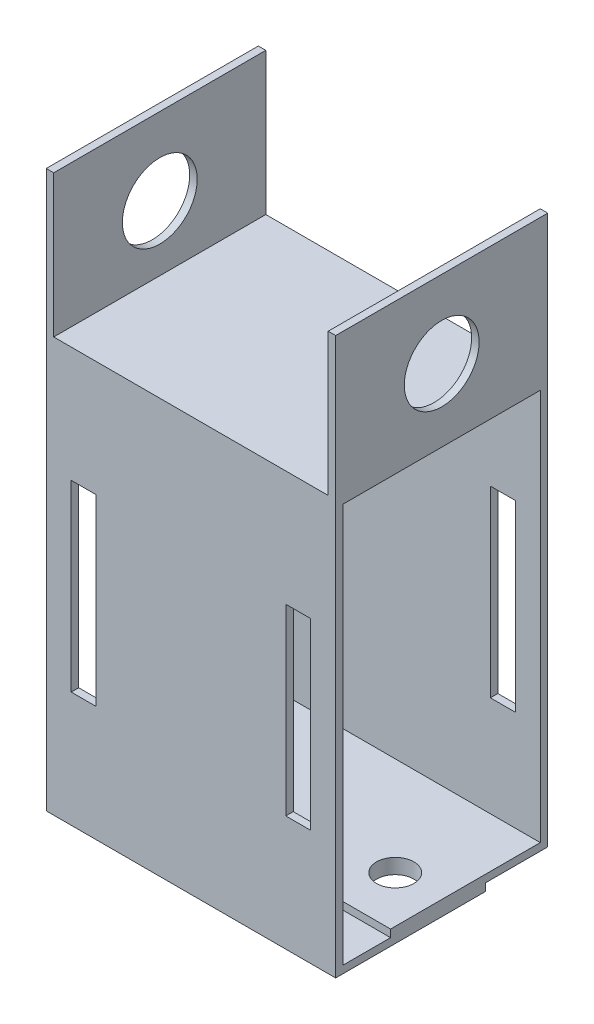
SolidWorks part; units mm, degrees
material "6061 Alloy"
ref_plane "Front Plane" through (0, 0, 0) normal (0, 0, 1) x (1, 0, 0)
ref_plane "Top Plane" through (0, 0, 0) normal (0, 1, 0) x (1, 0, 0)
ref_plane "Right Plane" through (0, 0, 0) normal (1, 0, 0) x (0, 0, -1)
sketch "Sketch1" plane through (0, 0, 0) normal (0, 1, 0) x (1, 0, 0)
  line L0 (0, -1000) -> (0, 49000) construction
  line L1 (13.97, -10.795) -> (-13.97, -10.795)
  line L2 (13.97, -10.795) -> (13.97, 10.795)
  line L3 (13.97, 10.795) -> (-13.97, 10.795)
  line L4 (-13.97, -10.795) -> (-13.97, 10.795)
  line L5 (13.97, -10.795) -> (-13.97, 10.795) construction
  line L6 (13.97, 10.795) -> (-13.97, -10.795) construction
  point P0 (0, 0)
  dimension "D1" = 21.59
  dimension "D2" = 27.94
extrude "Boss-Extrude1" add sketch "Sketch1" along normal blind 0.762
sketch "Sketch2" plane through (13.97, 0, 0) normal (1, 0, 0) x (0, 0, -1)
  line L0 (10.795, 0.762) -> (10.795, 0) construction
  line L1 (-10.795, 0) -> (10.795, 0)
  line L2 (-10.795, 0) -> (-10.795, 15.24)
  line L3 (-10.795, 15.24) -> (10.795, 15.24)
  line L4 (10.795, 0) -> (10.795, 15.24)
  circle A0 centre (0, 7.366) radius 3.81
  dimension "D2" = 7.62
  dimension "D1" = 15.24
  dimension "D3" = 7.366
extrude "Boss-Extrude2" add sketch "Sketch2" along normal blind 0.762
mirror "Mirror1" about plane through (0, 0, 0) normal (1, 0, 0) of "Boss-Extrude2"
sketch "Sketch3" plane through (0, 0, 10.795) normal (0, 0, 1) x (1, 0, 0)
  line L1 (-14.732, 0) -> (14.732, 0)
  line L2 (-14.732, 0) -> (-14.732, -40.64)
  line L3 (-14.732, -40.64) -> (14.732, -40.64)
  line L4 (14.732, 0) -> (14.732, -40.64)
  dimension "D1" = 40.64
extrude "Boss-Extrude3" add sketch "Sketch3" against normal blind 0.762
mirror "Mirror2" about plane through (0, 0, 0) normal (0, 0, 1) of "Boss-Extrude3"
sketch "Sketch4" plane through (0, -40.64, 0) normal (0, -1, 0) x (1, 0, 0)
  line L0 (14.732, 10.033) -> (14.732, 10.795) construction
  line L1 (-14.732, 10.795) -> (14.732, 10.795)
  line L2 (-14.732, 10.795) -> (-14.732, -4.445)
  line L3 (-14.732, -4.445) -> (14.732, -4.445)
  line L4 (14.732, 10.795) -> (14.732, -4.445)
  dimension "D1" = 15.24
extrude "Boss-Extrude4" add sketch "Sketch4" along normal blind 0.762
sketch "Sketch5" plane through (0, 0, -10.033) normal (0, 0, 1) x (1, 0, 0)
  line L0 (-14.732, 0) -> (-14.732, -40.64) construction
  line L1 (14.732, -40.64) -> (-14.732, -40.64)
  line L2 (14.732, -40.64) -> (14.732, -39.878)
  line L3 (14.732, -39.878) -> (-14.732, -39.878)
  line L4 (-14.732, -40.64) -> (-14.732, -39.878)
  dimension "D1" = 0.762
extrude "Boss-Extrude5" add sketch "Sketch5" along normal blind 15.24
sketch "Sketch6" plane through (0, -39.878, 0) normal (0, 1, 0) x (1, 0, 0)
  line L0 (-1000, 0) -> (49000, 0) construction
  line L1 (0, -1000) -> (0, 49000) construction
  circle A0 centre (10, 0) radius 1.905
  circle A1 centre (-10, 0) radius 1.905
  point P5 (0, 0)
  dimension "D1" = 3.81
  dimension "D2" = 10
extrude "Cut-Extrude1" cut sketch "Sketch6" against normal up to surface (1.524 mm away) up to face at (0, -41.402, 3.175)
sketch "Sketch7" plane through (0, 0, 10.795) normal (0, 0, 1) x (1, 0, 0)
  line L0 (14.732, -41.402) -> (-14.732, -41.402) construction
  line L1 (-9.652, -10.9855) -> (-12.192, -10.9855)
  line L2 (-9.652, -10.9855) -> (-9.652, -29.6545)
  line L3 (-9.652, -29.6545) -> (-12.192, -29.6545)
  line L4 (-12.192, -10.9855) -> (-12.192, -29.6545)
  line L6 (-14.732, 15.24) -> (-14.732, -41.402) construction
  line L7 (0, -1000) -> (0, 49000) construction
  line L8 (9.652, -29.6545) -> (12.192, -29.6545)
  line L9 (12.192, -10.9855) -> (12.192, -29.6545)
  line L10 (9.652, -10.9855) -> (12.192, -10.9855)
  line L11 (9.652, -10.9855) -> (9.652, -29.6545)
  dimension "D1" = 18.669
  dimension "D2" = 2.54
  dimension "D3" = 11.7475
  dimension "D4" = 2.54
extrude "Cut-Extrude2" cut sketch "Sketch7" against normal up to surface (21.59 mm away) up to face at (1.7463, -4.1593, -10.795)
